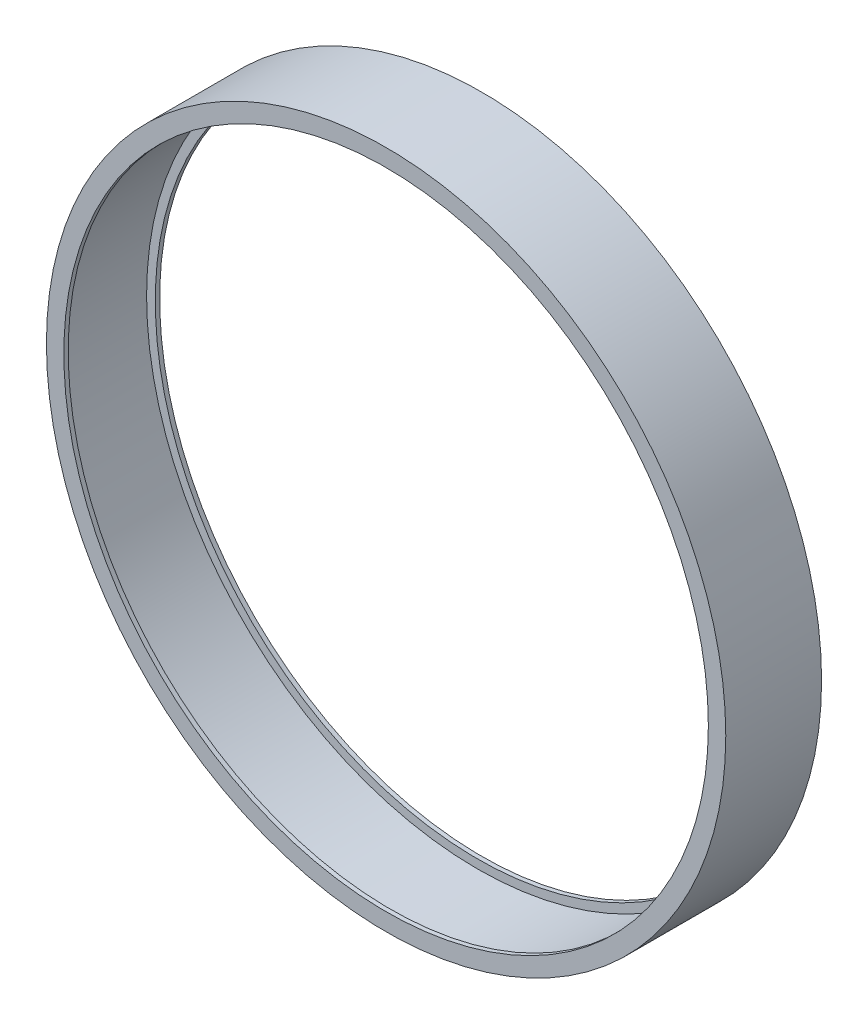
SolidWorks part; units mm, degrees
ref_plane "Front Plane" through (0, 0, 0) normal (0, 0, 1) x (1, 0, 0)
ref_plane "Top Plane" through (0, 0, 0) normal (0, 1, 0) x (1, 0, 0)
ref_plane "Right Plane" through (0, 0, 0) normal (1, 0, 0) x (0, 0, -1)
sketch "Sketch1" plane through (0, 0, 0) normal (0, 0, 1) x (1, 0, 0)
  circle A0 centre (0, 0) radius 37
  circle A1 centre (0, 0) radius 39
  circle A2 centre (0, 0) radius 38
  dimension "D1" = 2
  dimension "D2" = 1
extrude "Boss-Extrude1" add sketch "Sketch1" along normal mid plane 11 contours A1 | A0
extrude "Cut-Extrude1" cut sketch "Sketch1<7>" against normal mid plane 10 contours A2 | A0
sketch "Sketch1<7>" plane through (0, 0, 0) normal (0, 0, 1) x (1, 0, 0) same geometry as "Sketch1"
